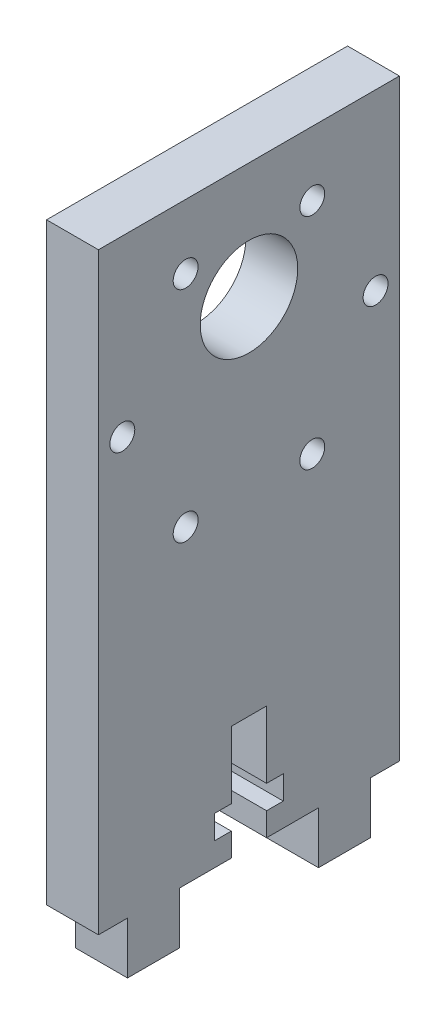
SolidWorks part; units mm, degrees
ref_plane "Front Plane" through (0, 0, 0) normal (0, 0, 1) x (1, 0, 0)
ref_plane "Top Plane" through (0, 0, 0) normal (0, 1, 0) x (1, 0, 0)
ref_plane "Right Plane" through (0, 0, 0) normal (1, 0, 0) x (0, 0, -1)
sketch "Motor plate" plane through (0, 0, 0) normal (1, 0, 0) x (0, 0, -1)
  line L0 (0, 15.0079) -> (7.747, 28.4261) construction
  line L1 (-18.415, -36.3001) -> (-14.859, -36.3001)
  line L2 (-18.415, -36.3001) -> (-18.415, 36.3001)
  line L3 (-18.415, 36.3001) -> (18.415, 36.3001)
  line L4 (18.415, -36.3001) -> (18.415, 36.3001)
  line L5 (-18.415, -36.3001) -> (18.415, 36.3001) construction
  line L6 (-18.415, 36.3001) -> (18.415, -36.3001) construction
  line L7 (14.859, -36.3001) -> (18.415, -36.3001)
  line L13 (0, 36.3001) -> (0, -24.5526) construction
  circle A0 centre (7.747, 28.4261) radius 1.524
  circle A1 centre (15.494, 15.0079) radius 1.524
  circle A2 centre (7.747, 1.5897) radius 1.524
  circle A3 centre (-7.747, 1.5897) radius 1.524
  circle A4 centre (-15.494, 15.0079) radius 1.524
  circle A5 centre (-7.747, 28.4261) radius 1.524
  circle A6 centre (0, 22.1199) radius 5.969
  circle A7 centre (0, 15.0079) radius 18.415 construction
  point P0 (0, 0)
  point P13 (0, -3.4071)
  point P15 (0, 15.0079)
  point P32 (0, 15.0079)
  line B0 (-8.509, -36.3001) -> (-8.509, -42.6501)
  line B1 (-8.509, -42.6501) -> (-14.859, -42.6501)
  line B2 (-14.859, -42.6501) -> (-14.859, -36.3001)
  line B3 (-2.159, -36.3001) -> (-2.159, -33.4324)
  line B4 (-2.159, -33.4324) -> (-4.2, -33.4324)
  line B5 (-4.2, -33.4324) -> (-4.2, -30.5324)
  line B6 (-4.2, -30.5324) -> (-2.159, -30.5324)
  line B7 (-2.159, -30.5324) -> (-2.159, -22.3301)
  line B8 (-2.159, -22.3301) -> (2.159, -22.3301)
  line B9 (2.159, -22.3301) -> (2.159, -30.5324)
  line B10 (2.159, -30.5324) -> (4.2, -30.5324)
  line B11 (4.2, -30.5324) -> (4.2, -33.4324)
  line B12 (4.2, -33.4324) -> (2.159, -33.4324)
  line B13 (2.159, -33.4324) -> (2.159, -36.3001)
  line B14 (0, -22.3301) -> (0, -36.3001) construction
  line B15 (8.509, -36.3001) -> (2.159, -36.3001)
  line B16 (14.859, -42.6501) -> (14.859, -36.3001)
  line B17 (-8.509, -36.3001) -> (-2.159, -36.3001)
  line B18 (8.509, -42.6501) -> (14.859, -42.6501)
  line B19 (8.509, -36.3001) -> (8.509, -42.6501)
  dimension "D3" = 30
  dimension "D4" = 15.494
  dimension "D5" = 3.048
  dimension "D8" = 11.938
  dimension "D2" = 36.83
  dimension "D1" = 58.42
  dimension "D6" = 6.35
  dimension "D7" = 6
  dimension "D9" = 7.112
sketch_block_instance "Male T-slot assembly-1"
sketch_block "Male T-slot assembly" parameters "D1"=6.35, "D2"=6.35, "D3"=4.318, "D4"=2.9, "D5"=8.4, "D6"=13.97, "D7"=6.35
extrude "Boss-Extrude1" add sketch "Motor plate" along normal blind 6.35 contours L3 | L4 L3 L2 A6 A5 A4 A3 A2 A1 A0 region at (0, -1.6502, 0)
equation "\"Ball Diameter\"= 1.75in"
equation "\"Sheet Thickness\"= 0.25in"
equation "\"Screw Diameter\"= .17in"
equation "\"Robot Diameter\"= 14in"
equation "\"Castor Screw Diameter\"= 0.22in"
equation "\"Wheel Diameter\" = 4in"
equation "\"Nut Diameter\" = 8.4mm"
equation "\"Nut Height\" = 2.9mm"
equation "\"Screw Height\" = 0.55in"
equation "\"D1@Boss-Extrude1\"=\"Sheet Thickness\""
equation "\"Ball Radius\" = \"Ball Diameter\"/2"
equation "\"Pulley Diameter\" = 1in"
equation "\"Reactor Height\" = 14in"
equation "\"Elevator Height\" = 11.5in"
equation "\"Elevator Width\" = \"Ball Diameter\" + 0.25in"
equation "\"Elevator Bearing Diameter\" = sqr(2*(\"Sheet Thickness\"^2)) + 0.2in"
equation "\"Elevator Axle Endcap Diameter\" = \"Pulley Diameter\" + 0.25in"
equation "\"Elevator Axle Length\" = \"Elevator Width\" + 8*\"Sheet Thickness\""
equation "\"Elevator Clearance from Axis\" = 3.5in"
equation "\"Elevator Horizontal Clearance\" = \"Elevator Width\" + 0.5in"
equation "\"Claw Horizontal Seperation\" = (\"Elevator Width\"/2) - (1.5 * \"Sheet Thickness\") - 0.15in"
equation "\"Claw Radius\" = \"Ball Radius\" + 0.1in"
equation "\"Castor Wheel Height\" = 1.25in"
